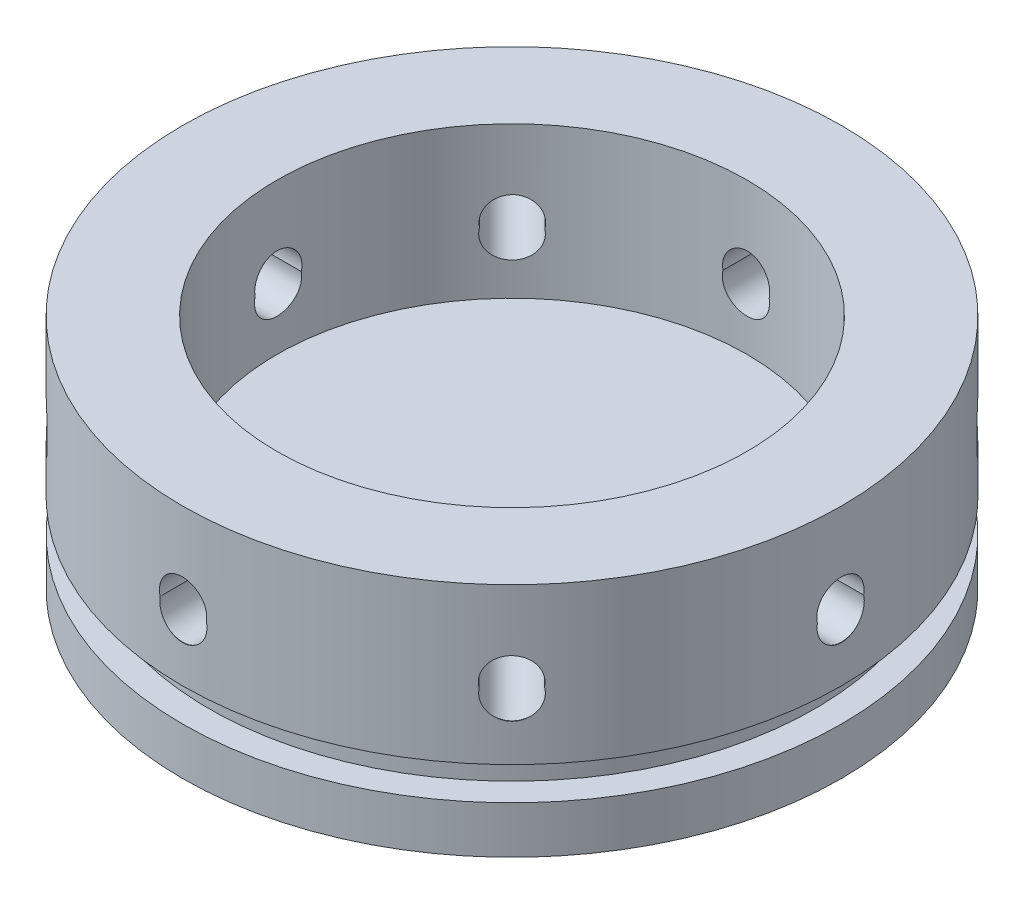
SolidWorks part; units mm, degrees
material "Liga 6061"
ref_plane "Plano frontal" through (0, 0, 0) normal (0, 0, 1) x (1, 0, 0)
ref_plane "Plano superior" through (0, 0, 0) normal (0, 1, 0) x (1, 0, 0)
ref_plane "Plano direito" through (0, 0, 0) normal (1, 0, 0) x (0, 0, -1)
sketch "Esboço1" plane through (0, 0, 0) normal (0, 0, 1) x (1, 0, 0)
  line L0 (0, 0) -> (0, 9)
  line L1 (0, 0) -> (-34.9, 0)
  line L2 (-34.9, 0) -> (-34.9, 3)
  line L3 (-34.9, 17.5) -> (-34.9, 25)
  line L4 (-34.9, 25) -> (-24.9, 25)
  line L5 (-24.9, 25) -> (-24.9, 9)
  line L6 (-34.9, 8.5) -> (-34.9, 17.5)
  line L7 (-34.9, 8.5) -> (-32.1, 8.5)
  line L8 (-24.9, 9) -> (0, 9)
  line L9 (0, 0) -> (0, 19.8802) construction
  line L10 (-34.9, 3) -> (-34.9, 5)
  line L11 (-34.9, 5) -> (-32.1, 5)
  line L12 (-32.1, 5) -> (-32.1, 8.5)
  line L13 (-24.9, 21) -> (-24.9, 16)
  dimension "D1" = 5
  dimension "D2" = 34.9
  dimension "D3" = 25
  dimension "D4" = 10
  dimension "D5" = 16
  dimension "D6" = 3.5
  dimension "D7" = 2.8
  dimension "D8" = 2.8
revolve "Revolução1" add sketch "Esboço1" angle 360 about L9 region at (-21.4016, 8.7601, 0)
ref_plane "Plano1" through (-34.9, 0, 0) normal (-1, 0, 0) x (0, 0, 1)
hole_wizard "Broca de rosquear para tarraxa de M6x1.01" positions "Esboço3" profile "Esboço4" hole size "M6x1.0" standard "Ansi Metric" end condition up to next
sketch "Esboço3" plane through (-34.9, 0, 0) normal (-1, 0, 0) x (0, 0, 1)
  line L0 (24.9, 25) -> (-24.9, 25) construction
  point P0 (0, 15)
  dimension "D1" = 10
sketch "Esboço4" plane through (-34.9, 15, 0) normal (0, 1, 0) x (0, 0, 1)
  line L0 (0, 0) -> (0, 10)
  line L1 (0, 10) -> (2.5, 10)
  line L2 (2.5, 10) -> (2.5, 0.025)
  line L3 (2.5, 0.025) -> (2.525, 0)
  line L5 (2.525, 0) -> (0, 0)
  line L6 (-2.5, 0.025) -> (-2.525, 0) construction
  line L11 (0, -6.35) -> (0, 107.95) construction
  dimension "Thru Hole Dia." = 5
  dimension "Thru Hole Depth" = 10
  dimension "Near C'Sink Dia." = 5.05
  dimension "Near C'Sink Angle" = 90
pattern_circular "PadrãoCircular2" count 8 over 360 about axis through (0, 25, 0) along (0, -1, 0) of "Broca de rosquear para tarraxa de M6x1.01"
sketch "Esboço2" plane through (-34.9, 0, 0) normal (-1, 0, 0) x (0, 0, 1)
  line L0 (0, 0) -> (0, 36.2111) construction
  line L1 (24.9, 25) -> (-24.9, 25) construction
  circle A0 centre (-0.0267, 16) radius 2.5
  dimension "D1" = 5
  dimension "D2" = 9
extrude "Corte-extrusão1" cut sketch "Esboço2" against normal up to next
pattern_circular "PadrãoCircular1" count 8 over 360 about axis through (0, 25, 0) along (0, -1, 0) of "Corte-extrusão1"
